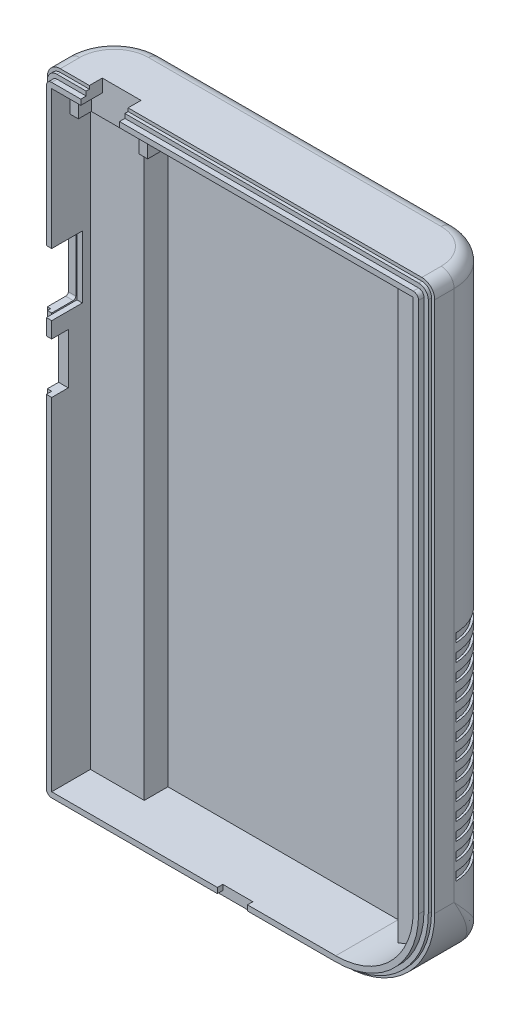
SolidWorks part; units mm, degrees
ref_plane "Front Plane" through (0, 0, 0) normal (0, 0, 1) x (1, 0, 0)
ref_plane "Top Plane" through (0, 0, 0) normal (0, 1, 0) x (1, 0, 0)
ref_plane "Right Plane" through (0, 0, 0) normal (1, 0, 0) x (0, 0, -1)
sketch "Sketch1" plane through (0, 0, 0) normal (0, 0, 1) x (1, 0, 0)
  line L1 (-45, 73.75) -> (45, 73.75)
  line L2 (-45, 73.75) -> (-45, -73.75)
  line L3 (-45, -73.75) -> (45, -73.75)
  line L4 (45, 73.75) -> (45, -73.75)
  line L5 (-45, 73.75) -> (45, -73.75) construction
  line L6 (-45, -73.75) -> (45, 73.75) construction
  point P0 (0, 0)
  dimension "D1" = 90
  dimension "D2" = 147.5
extrude "Body" add sketch "Sketch1" along normal mid plane 17.5
fillet "Lower Corner Curve" radius 21 1 edges at (45, -73.75, 0)
fillet "Rounded Back" radius 11 2 edges at (-45, 0, -8.75) (45, 10.5, -8.75)
shell "Shell" thickness 3
fillet "Rounded Top/Bottom" radius 3 10 edges at (45, 73.75, 5.5) (41.7782, 73.75, -5.5282) (-45, 73.75, 5.5) (-41.7782, 73.75, -5.5282) (0, 73.75, -8.75) (-45, -73.75, 5.5) (-41.7782, -73.75, -5.5282) (41.514, -64.3371, -5.7837) (29.158, -73.1067, -8.75) (-5, -73.75, -8.75)
sketch "Sketch13" plane through (0, 0, 8.75) normal (0, 0, 1) x (1, 0, 0)
  line L5 (42, 70.75) -> (-42, 70.75) construction
  line L6 (42, -52.75) -> (42, 70.75) construction
  line L7 (-42, 70.75) -> (-42, -70.75) construction
  line L8 (-42, -70.75) -> (24, -70.75) construction
  line L9 (-42, -70.75) -> (24, -70.75)
  line L10 (-42, 70.75) -> (-42, -70.75)
  line L11 (42, -52.75) -> (42, 70.75)
  line L12 (42, 70.75) -> (-42, 70.75)
  arc A2 (24, -70.75) -> (42, -52.75) centre (24, -52.75) ccw construction
  arc A3 (24, -70.75) -> (42, -52.75) centre (24, -52.75) ccw
extrude "Square Shell Cut" cut sketch "Sketch13" against normal blind 12
sketch "Sketch2" plane through (0, 0, 8.75) normal (0, 0, 1) x (1, 0, 0)
  line L0 (-44.25, 70.75) -> (-44.25, -70.75)
  line L1 (-42, -73) -> (24, -73)
  line L2 (44.25, -52.75) -> (44.25, 70.75)
  line L3 (42, 73) -> (-42, 73)
  line L4 (-45, 70.75) -> (-45, -70.75)
  line L5 (-42, -73.75) -> (24, -73.75)
  line L6 (45, -52.75) -> (45, 70.75)
  line L7 (42, 73.75) -> (-42, 73.75)
  line L8 (-45, 70.75) -> (-45, -70.75)
  line L9 (-42, -73.75) -> (24, -73.75)
  line L10 (45, -52.75) -> (45, 70.75)
  line L11 (42, 73.75) -> (-42, 73.75)
  arc A0 (-44.25, -70.75) -> (-42, -73) centre (-42, -70.75) ccw
  arc A1 (24, -73) -> (44.25, -52.75) centre (24, -52.75) ccw
  arc A2 (44.25, 70.75) -> (42, 73) centre (42, 70.75) ccw
  arc A3 (-42, 73) -> (-44.25, 70.75) centre (-42, 70.75) ccw
  arc A4 (-45, -70.75) -> (-42, -73.75) centre (-42, -70.75) ccw
  arc A5 (24, -73.75) -> (45, -52.75) centre (24, -52.75) ccw
  arc A6 (45, 70.75) -> (42, 73.75) centre (42, 70.75) ccw
  arc A7 (-42, 73.75) -> (-45, 70.75) centre (-42, 70.75) ccw
  arc A8 (-45, -70.75) -> (-42, -73.75) centre (-42, -70.75) ccw
  arc A9 (24, -73.75) -> (45, -52.75) centre (24, -52.75) ccw
  arc A10 (45, 70.75) -> (42, 73.75) centre (42, 70.75) ccw
  arc A11 (-42, 73.75) -> (-45, 70.75) centre (-42, 70.75) ccw
  dimension "D1" = 0
  dimension "D2" = 0.75
extrude "Front Edge 1" cut sketch "Sketch2" against normal blind 2
sketch "Sketch3" plane through (0, 0, 8.75) normal (0, 0, 1) x (1, 0, 0)
  line L0 (42, 72) -> (-42, 72)
  line L1 (-43.25, 70.75) -> (-43.25, -70.75)
  line L2 (-42, -72) -> (24, -72)
  line L3 (43.25, -52.75) -> (43.25, 70.75)
  line L4 (42, 73) -> (-42, 73)
  line L5 (42, 73) -> (-42, 73)
  line L6 (-44.25, 70.75) -> (-44.25, -70.75)
  line L7 (-44.25, 70.75) -> (-44.25, -70.75)
  line L8 (-42, -73) -> (24, -73)
  line L9 (-42, -73) -> (24, -73)
  line L10 (44.25, -52.75) -> (44.25, 70.75)
  line L11 (44.25, -52.75) -> (44.25, 70.75)
  line L13 (42, 73) -> (-42, 73) construction
  arc A0 (-42, 72) -> (-43.25, 70.75) centre (-42, 70.75) ccw
  arc A1 (-43.25, -70.75) -> (-42, -72) centre (-42, -70.75) ccw
  arc A2 (24, -72) -> (43.25, -52.75) centre (24, -52.75) ccw
  arc A3 (43.25, 70.75) -> (42, 72) centre (42, 70.75) ccw
  arc A4 (-42, 73) -> (-44.25, 70.75) centre (-42, 70.75) ccw
  arc A5 (-42, 73) -> (-44.25, 70.75) centre (-42, 70.75) ccw
  arc A9 (-44.25, -70.75) -> (-42, -73) centre (-42, -70.75) ccw
  arc A10 (-44.25, -70.75) -> (-42, -73) centre (-42, -70.75) ccw
  arc A11 (24, -73) -> (44.25, -52.75) centre (24, -52.75) ccw
  arc A12 (24, -73) -> (44.25, -52.75) centre (24, -52.75) ccw
  arc A14 (44.25, 70.75) -> (42, 73) centre (42, 70.75) ccw
  arc A15 (44.25, 70.75) -> (42, 73) centre (42, 70.75) ccw
  dimension "D2" = 1.25
  dimension "D1" = 0
extrude "Front Edge 2" cut sketch "Sketch3" against normal blind 1.25
sketch "Sketch11" plane through (0, 73.75, 0) normal (0, 1, 0) x (1, 0, 0)
  line L0 (-34, 8.75) -> (34, 8.75) construction
  line L1 (-34, 8.75) -> (34, 8.75)
  line L2 (-34, 8.25) -> (34, 8.25)
  line L3 (45, -2.25) -> (42, -2.25) construction
  line L5 (44.4881, -1.75) -> (44.9886, -1.75)
  line L6 (-44.9886, -1.75) -> (-44.4881, -1.75)
  arc A0 (45, -2.25) -> (34, 8.75) centre (34, -2.25) ccw construction
  arc A1 (-34, 8.75) -> (-45, -2.25) centre (-34, -2.25) ccw construction
  arc A2 (44.9886, -1.75) -> (34, 8.75) centre (34, -2.25) ccw
  arc A3 (-34, 8.75) -> (-44.9886, -1.75) centre (-34, -2.25) ccw
  arc A4 (-34, 8.25) -> (-44.4881, -1.75) centre (-34, -2.25) ccw
  arc A5 (44.4881, -1.75) -> (34, 8.25) centre (34, -2.25) ccw
  arc A6 (-34, 8.75) -> (-45, -2.25) centre (-34, -2.25) ccw construction
  arc A7 (-34, 8.25) -> (-44.5, -2.25) centre (-34, -2.25) ccw construction
  arc A8 (45, -2.25) -> (34, 8.75) centre (34, -2.25) ccw construction
  arc A9 (44.5, -2.25) -> (34, 8.25) centre (34, -2.25) ccw construction
  point P16 (0, 0)
  point P17 (44.7384, -1.75)
  dimension "D2" = 0.5
  dimension "D1" = 0.5
extrude "Grip Cut" cut sketch "Sketch11" against normal blind 2 from offset 72.5 offset against normal yes
pattern_linear "Grip Pattern" count 13 spacing 4 along (0, -1, 0) of "Grip Cut"
ref_plane "Back Support Plane" through (0, 0, -0.25) normal (0, 0, 1) x (1, 0, 0)
sketch "Sketch12" plane through (0, 0, -0.25) normal (0, 0, 1) x (1, 0, 0)
  line L0 (-29.5, 40.3846) -> (-29.5, 13.2433)
  line L1 (-42, 70.75) -> (-42, -70.75) construction
  dimension "D1" = 12.5
rib "Left Support Rib" sketch "Sketch12" sketch "Sketch12" thickness 12.5 extrusion direction normal to sketch draft on no parameters "D1"=12.5
sketch "Sketch14" plane through (0, 0, -0.25) normal (0, 0, 1) x (1, 0, 0)
  line L0 (29.5, 31.4261) -> (29.5, -7.5766)
  line L2 (42, -52.75) -> (42, 70.75) construction
  dimension "D1" = 12.5
rib "Rib3" sketch "Sketch14" sketch "Sketch14" thickness 12.5 parameters "D1"=12.5
sketch "Sketch15" plane through (0, 0, 8.75) normal (0, 0, 1) x (1, 0, 0)
  line L0 (-3.5, -72) -> (-3.5, -70.75)
  line L4 (-42, -70.75) -> (24, -70.75) construction
  line L6 (3.5, -72) -> (-3.5, -72)
  line L7 (-3.5, -70.75) -> (3.5, -70.75)
  line L8 (3.5, -70.75) -> (3.5, -72)
  line L9 (0, -9.625) -> (0, 9.625) construction
  line L11 (-42, -72) -> (24, -72) construction
  line L13 (-42, -70.75) -> (24, -70.75) construction
  point P9 (0, -70.75)
  point P11 (0, -72)
  point P12 (0, 0)
  dimension "D1" = 7
extrude "Audio Jack slot" cut sketch "Sketch15" against normal up to surface (1.25 mm away) up to face at (-1.784, 1.784, 7.5)
sketch "Sketch16" plane through (-45, 0, 0) normal (-1, 0, 0) x (0, 0, 1)
  line L0 (8.75, 70.75) -> (8.75, -70.75) construction
  line L1 (8.75, 38.25) -> (8.75, 24.35)
  line L2 (1.9, 38.25) -> (8.75, 38.25)
  line L3 (1.9, 38.25) -> (1.9, 24.35)
  line L4 (1.9, 24.35) -> (8.75, 24.35)
  line L5 (6.75, 70.75) -> (2.25, 70.75) construction
  point P6 (5.325, 38.25)
  dimension "D1" = 6.85
  dimension "D2" = 13.9
  dimension "D3" = 32.5
extrude "Cut-Extrude10" cut sketch "Sketch16" against normal up to vertex
sketch "Sketch17" plane through (-42, 0, 0) normal (1, 0, 0) x (0, 0, -1)
  line L0 (-8.75, 70.75) -> (-8.75, 38.25) construction
  line L1 (-8.75, 38.55) -> (-1.63, 38.55)
  line L2 (-8.75, 38.55) -> (-8.75, 24.05)
  line L3 (-8.75, 24.05) -> (-1.63, 24.05)
  line L4 (-1.63, 38.55) -> (-1.63, 24.05)
  line L5 (-8.75, 38.25) -> (-1.9, 38.25) construction
  dimension "D1" = 7.12
  dimension "D2" = 14.5
  dimension "D3" = 0.3
extrude "Cut-Extrude11" cut sketch "Sketch17" along direction (-1, 0, 0) on the side against the normal up to surface (1.25 mm away)
fillet "Fillet9" radius 0.6 2 edges at (-44.1222, 24.35, 1.9) (-44.1222, 38.25, 1.9)
sketch "Sketch18" plane through (-45, 0, 0) normal (-1, 0, 0) x (0, 0, 1)
  line L1 (4.9, 20.35) -> (8.75, 20.35)
  line L2 (4.9, 20.35) -> (4.9, 8.6)
  line L3 (4.9, 8.6) -> (8.75, 8.6)
  line L4 (2.5, 24.35) -> (6.75, 24.35) construction
  line L6 (8.75, 24.05) -> (8.75, -70.75) construction
  line L10 (8.75, 20.35) -> (8.75, 8.6)
  dimension "D1" = 3.85
  dimension "D2" = 11.75
  dimension "D3" = 4
extrude "Cut-Extrude12" cut sketch "Sketch18" against normal up to vertex (3 mm away) up to point (-42, 24.05, 8.75)
sketch "Sketch19" plane through (-45, 0, 0) normal (-1, 0, 0) x (0, 0, 1)
  line L1 (6.75, 22.35) -> (-8.75, 22.35)
  line L2 (6.75, 22.35) -> (6.75, 6.6)
  line L3 (6.75, 6.6) -> (-8.75, 6.6)
  line L4 (-8.75, 22.35) -> (-8.75, 6.6)
  line L5 (-8.75, 1.25) -> (-8.75, 70.75) construction
  line L6 (6.75, 20.35) -> (4.9, 20.35) construction
  line L7 (4.9, 8.6) -> (6.75, 8.6) construction
  line L8 (6.75, 24.35) -> (6.75, 20.35) construction
  point P4 (0, 0)
  dimension "D1" = 2
  dimension "D2" = 2
extrude "Cut-Extrude13" cut sketch "Sketch19" against normal up to surface (0.75 mm away) up to face at (-44.25, 22.35, 7.125)
fillet "Fillet10" radius 0.75 4 edges at (-44.8109, 6.6, 0.219) (-44.8109, 22.35, 0.219) (-45, 6.6, 4.5) (-45, 22.35, 4.5)
sketch "Sketch21" plane through (0, 70.75, 0) normal (0, -1, 0) x (1, 0, 0)
  line L0 (42, 8.75) -> (-42, 8.75) construction
  line L1 (-35.25, 8.75) -> (-26.25, 8.75)
  line L2 (-35.25, 8.75) -> (-35.25, 3.75)
  line L3 (-35.25, 3.75) -> (-26.25, 3.75)
  line L4 (-26.25, 8.75) -> (-26.25, 3.75)
  line L5 (-42, 8.75) -> (-42, -0.25) construction
  dimension "D1" = 6.75
  dimension "D2" = 9
  dimension "D3" = 5
extrude "Power Switch Slot" cut sketch "Sketch21" against normal up to surface (3 mm away) up to face at (0, 73.75, 0.531)
sketch "Sketch22" plane through (0, 70.75, 0) normal (0, -1, 0) x (1, 0, 0)
  line L0 (-21.7, -5.75) -> (-21.7, 6.75)
  line L1 (29.5, -5.75) -> (-29.5, -5.75) construction
  line L2 (-21.7, 6.75) -> (-23.7, 6.75)
  line L3 (-23.7, 6.75) -> (-23.7, 3.75)
  line L4 (-23.7, 3.75) -> (-37.8, 3.75)
  line L5 (-37.8, 3.75) -> (-37.8, 6.75)
  line L6 (-37.8, 6.75) -> (-39.8, 6.75)
  line L7 (-39.8, 6.75) -> (-39.8, -0.25)
  line L8 (-29.5, -0.25) -> (-42, -0.25) construction
  line L9 (-29.5, -0.25) -> (-39.8, -0.25)
  line L10 (-29.5, -0.25) -> (-29.5, -5.75)
  line L11 (-35.25, 3.75) -> (-26.25, 3.75) construction
  line L12 (-29.5, -5.75) -> (-21.7, -5.75)
  point P7 (-30.75, 3.75)
  point P14 (-30.75, 3.75)
  dimension "D1" = 14.1
  dimension "D2" = 2
  dimension "D3" = 3
extrude "Boss-Extrude4" add sketch "Sketch22" along normal blind 5
